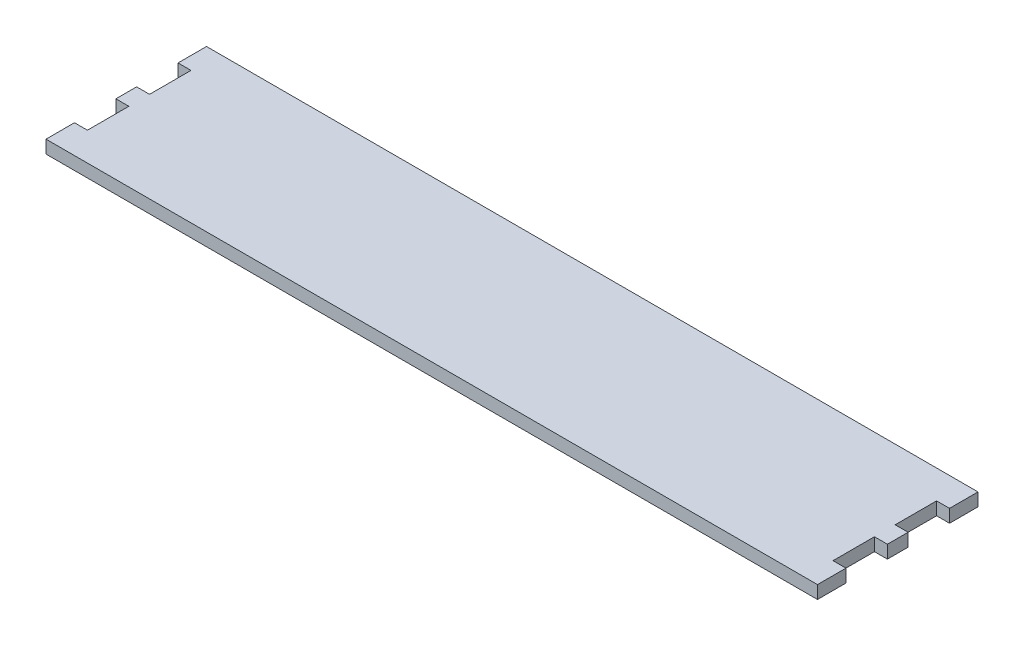
SolidWorks part; units mm, degrees
ref_plane "Front Plane" through (0, 0, 0) normal (0, 0, 1) x (1, 0, 0)
ref_plane "Top Plane" through (0, 0, 0) normal (0, 1, 0) x (1, 0, 0)
ref_plane "Right Plane" through (0, 0, 0) normal (1, 0, 0) x (0, 0, -1)
sketch "Sketch1" plane through (0, 0, 0) normal (0, 1, 0) x (1, 0, 0)
  line L0 (-39.6776, -21.9061) -> (-39.6776, -14.9211) construction
  line L1 (-42.8526, 17.4639) -> (146.3774, 17.4639)
  line L2 (-42.8526, 17.4639) -> (-42.8526, 10.4789)
  line L3 (-42.8526, -21.9061) -> (146.3774, -21.9061)
  line L4 (146.3774, 17.4639) -> (146.3774, 10.4789)
  line L5 (-42.8526, -2.2211) -> (-49.6362, -2.2211) construction
  line L6 (-39.6776, 17.4639) -> (-39.6776, 10.4789) construction
  line L7 (-42.8526, 0.3189) -> (-42.8526, -4.7611)
  line L8 (-39.6776, 10.4789) -> (-42.8526, 10.4789)
  line L9 (-39.6776, 10.4789) -> (-39.6776, 0.3189)
  line L10 (-39.6776, 0.3189) -> (-42.8526, 0.3189)
  line L11 (-39.6776, -4.7611) -> (-42.8526, -4.7611)
  line L12 (-39.6776, -14.9211) -> (-42.8526, -14.9211)
  line L13 (-39.6776, -14.9211) -> (-39.6776, -4.7611)
  line L14 (51.7624, 17.4639) -> (51.7624, -21.9061) construction
  line L15 (143.2024, -14.9211) -> (146.3774, -14.9211)
  line L16 (143.2024, -14.9211) -> (143.2024, -4.7611)
  line L17 (143.2024, -4.7611) -> (146.3774, -4.7611)
  line L18 (143.2024, 0.3189) -> (146.3774, 0.3189)
  line L19 (143.2024, 10.4789) -> (143.2024, 0.3189)
  line L20 (143.2024, 10.4789) -> (146.3774, 10.4789)
  line L21 (-42.8526, -14.9211) -> (-42.8526, -21.9061)
  line L22 (146.3774, -14.9211) -> (146.3774, -21.9061)
  line L23 (146.3774, 0.3189) -> (146.3774, -4.7611)
  dimension "D1" = 39.37
  dimension "D2" = 189.23
  dimension "D4" = 3.175
  dimension "D5" = 10.16
  dimension "D6" = 5.08
extrude "Boss-Extrude1" add sketch "Sketch1" along normal blind 3.175 contours L1 L4 L20 L19 L18 L23 L17 L16 L15 L22 L3 L21 L12 L13 L11 L7 L10 L9 L8 L2
